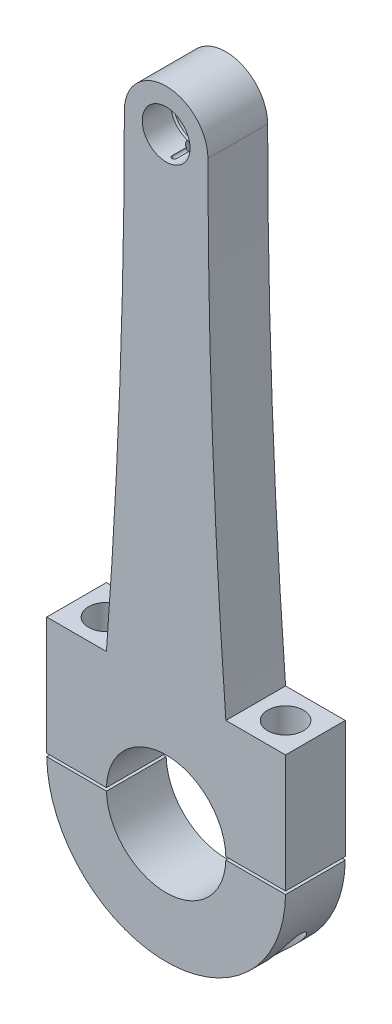
SolidWorks part; units mm, degrees
note: The reader was unsure of these and kept them because the rebuilt part matched: shared geometry of "Sketch2<2>", "Sketch5<5>".
ref_plane "Front Plane" through (0, 0, 0) normal (0, 0, 1) x (1, 0, 0)
ref_plane "Top Plane" through (0, 0, 0) normal (0, 1, 0) x (1, 0, 0)
ref_plane "Right Plane" through (0, 0, 0) normal (1, 0, 0) x (0, 0, -1)
sketch "Sketch1" plane through (0, 0, 0) normal (0, 0, 1) x (1, 0, 0)
  line L1 (-20, 0.25) -> (-20, 20)
  line L2 (20, 0.25) -> (20, 20)
  line L3 (-20, 20) -> (-10, 20)
  line L4 (-20, 0.25) -> (-9.9969, 0.25)
  line L5 (-19.9984, -0.25) -> (-9.9969, -0.25)
  line L6 (0, -0.25) -> (0, 0) construction
  line L7 (0, 0) -> (0, 0.25) construction
  line L8 (9.9969, -0.25) -> (19.9984, -0.25)
  line L9 (9.9969, 0.25) -> (20, 0.25)
  line L10 (-9.9969, 0.25) -> (0, 0.25) construction
  line L11 (0, 0.25) -> (9.9969, 0.25) construction
  line L12 (9.9969, -0.25) -> (0, -0.25) construction
  line L13 (0, -0.25) -> (-9.9969, -0.25) construction
  line L14 (-7, 100) -> (-4, 100) construction
  line L15 (7, 100) -> (7, 107) construction
  line L16 (-7, 100) -> (-7, 107) construction
  line L17 (-7, 107) -> (7, 107) construction
  line L18 (10, 20) -> (20, 20)
  line L19 (-10, 20) -> (10, 20) construction
  arc A0 (-9.9969, -0.25) -> (9.9969, -0.25) centre (0, 0) ccw
  arc A1 (-19.9984, -0.25) -> (19.9984, -0.25) centre (0, 0) ccw
  arc A2 (9.9969, 0.25) -> (-9.9969, 0.25) centre (0, 0) ccw
  circle A3 centre (0, 100) radius 4
  arc A4 (7, 100) -> (-7, 100) centre (0, 100) ccw
  arc A5 (7, 100) -> (10, 20) centre (1075.1667, 100) ccw
  arc A6 (-7, 100) -> (-10, 20) centre (-1075.1667, 100) cw
  arc A7 (-9.9969, 0.25) -> (-9.9969, -0.25) centre (0, 0) ccw construction
  arc A8 (9.9969, 0.25) -> (9.9969, -0.25) centre (0, 0) cw construction
  point P1 (0, 0)
  point P4 (0, 20)
  point P27 (-10, 0)
  point P28 (-10, 0)
  point P29 (13.803, 0)
  point P30 (0, 0)
  point P31 (0, 0)
  point P32 (10.3173, 0)
  point P33 (0, 0)
  dimension "D2" = 10
  dimension "D3" = 10
  dimension "D4" = 8
  dimension "D5" = 3
  dimension "D1" = 0.5
  dimension "D6" = 100
extrude "Boss-Extrude1" add sketch "Sketch1" along normal blind 10
sketch "Sketch2" plane through (0, 20, 0) normal (0, 1, 0) x (1, 0, 0)
  line L0 (20, -10) -> (10, -10) construction
  line L3 (20, 0) -> (10, 0) construction
  line L4 (10, -10) -> (10, 0) construction
  line L5 (0, 0) -> (0, -10) construction
  circle A0 centre (15, -5) radius 5 construction
  circle A1 centre (15, -5) radius 3
  circle A2 centre (-15, -5) radius 3
  circle A3 centre (15, -5) radius 2.5
  circle A4 centre (-15, -5) radius 2.5
  point P10 (0, 0)
  dimension "D1" = 10
  dimension "D2" = 6
  dimension "D3" = 5
extrude "Cut-Extrude1" cut sketch "Sketch2" against normal up to vertex (19.75 mm away)
extrude "Cut-Extrude2" cut sketch "Sketch2<2>" against normal through all contours A4 | A3
sketch "Sketch2<2>" plane through (0, 20, 0) normal (0, 1, 0) x (1, 0, 0) same geometry as "Sketch2"
ref_plane "Plane1" through (0, 10, 0) normal (0, -1, 0) x (-1, 0, 0)
sketch "Sketch3" plane through (0, 10, 0) normal (0, -1, 0) x (-1, 0, 0)
  line L0 (0, -10) -> (0, -5) construction
  line L1 (0, -5) -> (0, 0) construction
  line L2 (-9.9969, -10) -> (9.9969, -10) construction
  circle A0 centre (0, -5) radius 1.25
  dimension "D1" = 2.5
extrude "Cut-Extrude3" cut sketch "Sketch3" against normal up to next and the other way up to surface other way up to face at (0, 5.125, 5)
sketch "Sketch5" plane through (0, 0, 0) normal (1, 0, 0) x (0, 0, -1)
  line L0 (-1, 96) -> (-9, 96)
  line L1 (-3.75, 96) -> (0, 96) construction
  line L2 (-10, 96) -> (-6.25, 96) construction
  line L3 (-8.6, 95.6) -> (-1.4, 95.6)
  line L4 (-10, 96) -> (-6.25, 96) construction
  line L5 (-5, 95.6) -> (-4.7691, 96)
  line L6 (-5, 95.6) -> (-5.2309, 96)
  line L7 (-10, 100) -> (-10, 20) construction
  line L8 (-10, 96) -> (-9, 96) construction
  line L9 (-1, 96) -> (0, 96) construction
  line L10 (-3.75, 96) -> (0, 96) construction
  line L11 (-10, 104) -> (-10, 96) construction
  line L12 (0, 96) -> (0, 104) construction
  arc A0 (-8.6, 95.6) -> (-9, 96) centre (-8.6, 96) cw
  arc A1 (-1.4, 95.6) -> (-1, 96) centre (-1.4, 96) ccw
  dimension "D3" = 0.4
  dimension "D1" = 60
  dimension "D2" = 1
revolve "Cut-Revolve1" cut sketch "Sketch5" angle 360 about L8
ref_axis "Axis1" through (0, 100, 10) along (0, 0, -1)
revolve "Cut-Revolve2" cut sketch "Sketch5<5>" angle 360 about axis through (0, 100, 10) along (0, 0, -1)
sketch "Sketch5<5>" plane through (0, 0, 0) normal (1, 0, 0) x (0, 0, -1) same geometry as "Sketch5"
ref_plane "Plane2" through (0, 0, 5) normal (0, 0, 1) x (1, 0, 0)
sketch "Sketch6" plane through (0, 0, 5) normal (0, 0, 1) x (1, 0, 0)
  circle A0 centre (0, 100) radius 4
  arc A1 (1.2285, 96.1933) -> (-1.2285, 96.1933) centre (0, 100) ccw construction
